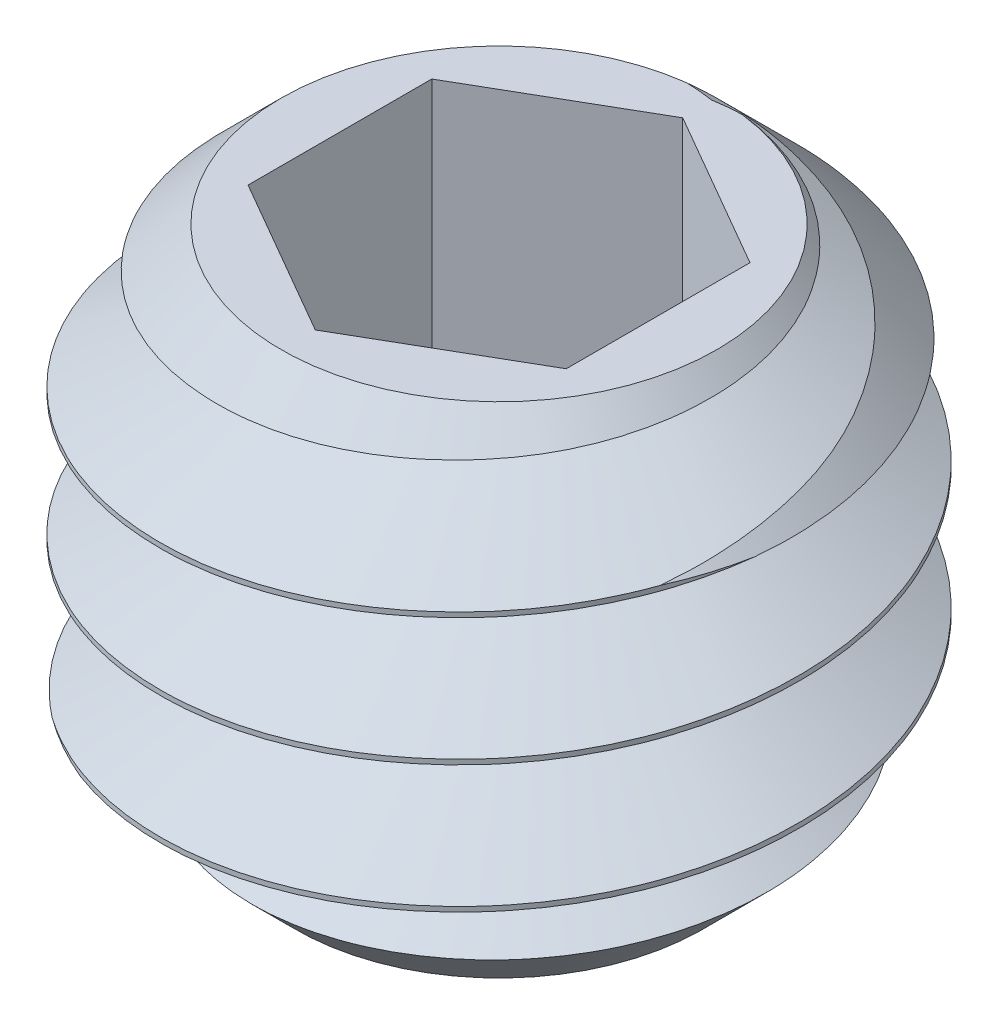
SolidWorks part; units mm, degrees
ref_plane "Front Plane" through (0, 0, 0) normal (0, 0, 1) x (1, 0, 0)
ref_plane "Top Plane" through (0, 0, 0) normal (0, 1, 0) x (1, 0, 0)
ref_plane "Right Plane" through (0, 0, 0) normal (1, 0, 0) x (0, 0, -1)
sketch "Sketch1" plane through (0, 0, 0) normal (0, 0, 1) x (1, 0, 0)
  line L0 (0, 0) -> (0, 54.6222) construction
  line L1 (0, 0.5866) -> (-1.016, 0)
  line L2 (-1.016, 0) -> (-1.27, 0)
  line L3 (-1.27, 0) -> (-1.9939, 0.7239)
  line L4 (-1.9939, 0.7239) -> (-1.9939, 2.54)
  line L5 (-1.9939, 2.54) -> (-1.3589, 3.175)
  line L6 (-1.3589, 3.175) -> (0, 3.175)
  line L7 (0, 3.175) -> (0, 0.5866)
  dimension "D1" = 60
  dimension "D2" = 2.032
  dimension "D3" = 135
  dimension "D4" = 135
  dimension "D5" = 0.635
  dimension "D6" = 3.9878
  dimension "D7" = 0.254
  dimension "D8" = 3.175
revolve "Revolve1" add sketch "Sketch1" angle 360 about L0
sketch "Sketch2" plane through (0, 3.175, 0) normal (0, 1, 0) x (1, 0, 0)
  line L0 (0, 0) -> (0, 1.3178) construction
  line L1 (0, 1.1457) -> (-0.9922, 0.5728)
  line L2 (-0.9922, 0.5728) -> (-0.9922, -0.5728)
  line L3 (-0.9922, -0.5728) -> (0, -1.1457)
  line L4 (0, -1.1457) -> (0.9922, -0.5728)
  line L5 (0.9922, -0.5728) -> (0.9922, 0.5728)
  line L6 (0.9922, 0.5728) -> (0, 1.1457)
  circle A0 centre (0, 0) radius 0.9922 construction
  dimension "D1" = 1.9844
extrude "Cut-Extrude1" cut sketch "Sketch2" against normal blind 1.778
sketch "Sketch3" plane through (0, 3.175, 0) normal (0, 1, 0) x (1, 0, 0)
  circle A0 centre (0, 0) radius 1.9939 construction
  circle A1 centre (0, 0) radius 1.9939
curve "Helix/Spiral1" pitch 0.795 height 9.525 radius 1.9939 centre (0, 3.175, 0) axis (0, -1, 0) start towards (0, 0, 1)
sketch "Sketch4" plane through (0, 0, 0) normal (1, 0, 0) x (0, 0, -1)
  line L0 (-2.0193, 3.9687) -> (-2.0193, 3.175)
  line L1 (-2.0193, 3.175) -> (-1.3319, 3.5719)
  line L2 (-1.3319, 3.5719) -> (-2.0193, 3.9687)
  line L3 (-1.3319, 3.5719) -> (-2.0193, 3.5719) construction
  line L5 (-2.0193, 3.9687) -> (-1.3319, 4.3656) construction
  line L6 (-1.3319, 4.3656) -> (-2.0193, 4.7625) construction
  line L7 (-2.0193, 4.7625) -> (-2.0193, 3.9687) construction
  line L8 (1.3589, 3.175) -> (-1.3589, 3.175) construction
  line L10 (0, 3.175) -> (0, 10.7636) construction
  dimension "D1" = 60
  dimension "D2" = 0.7937
  dimension "D3" = 4.0386
sweep "Cut-Sweep3" cut profiles "Sketch4" path "Helix/Spiral1"
